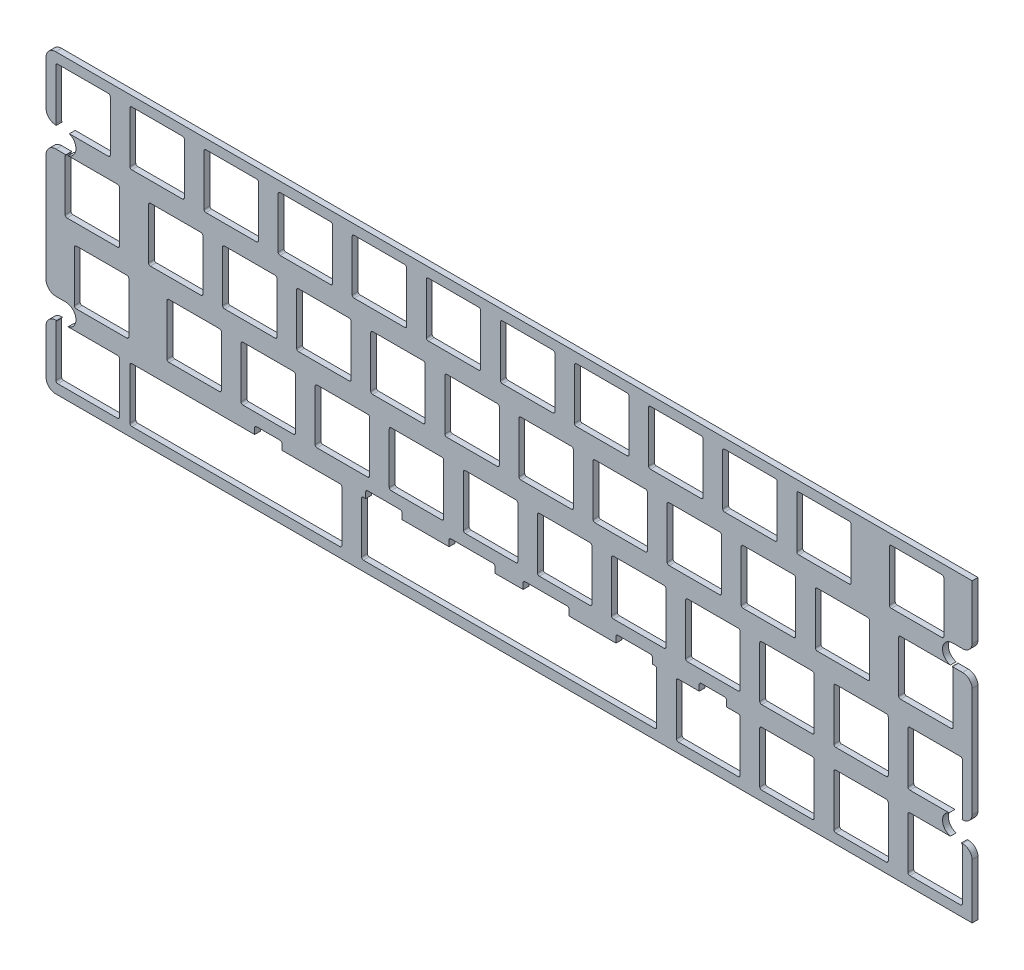
SolidWorks part; units mm, degrees
material "Brass"
ref_plane "Front Plane" through (0, 0, 0) normal (0, 0, 1) x (1, 0, 0)
ref_plane "Top Plane" through (0, 0, 0) normal (0, 1, 0) x (1, 0, 0)
ref_plane "Right Plane" through (0, 0, 0) normal (1, 0, 0) x (0, 0, -1)
sketch "Model" plane through (0, 0, 0) normal (0, 0, 1) x (1, 0, 0)
  line L0 (3.025, -2.525) -> (16.025, -2.525)
  line L1 (3.025, -16.525) -> (16.025, -16.525)
  line L2 (2.525, -3.025) -> (2.525, -16.025)
  line L3 (16.525, -3.025) -> (16.525, -16.025)
  line L4 (22.075, -2.525) -> (35.075, -2.525)
  line L5 (22.075, -16.525) -> (35.075, -16.525)
  line L6 (21.575, -3.025) -> (21.575, -16.025)
  line L7 (35.575, -3.025) -> (35.575, -16.025)
  line L8 (41.125, -2.525) -> (54.125, -2.525)
  line L9 (41.125, -16.525) -> (54.125, -16.525)
  line L10 (40.625, -3.025) -> (40.625, -16.025)
  line L11 (54.625, -3.025) -> (54.625, -16.025)
  line L12 (60.175, -2.525) -> (73.175, -2.525)
  line L13 (60.175, -16.525) -> (73.175, -16.525)
  line L14 (59.675, -3.025) -> (59.675, -16.025)
  line L15 (73.675, -3.025) -> (73.675, -16.025)
  line L16 (79.225, -2.525) -> (92.225, -2.525)
  line L17 (79.225, -16.525) -> (92.225, -16.525)
  line L18 (78.725, -3.025) -> (78.725, -16.025)
  line L19 (92.725, -3.025) -> (92.725, -16.025)
  line L20 (98.275, -2.525) -> (111.275, -2.525)
  line L21 (98.275, -16.525) -> (111.275, -16.525)
  line L22 (97.775, -3.025) -> (97.775, -16.025)
  line L23 (111.775, -3.025) -> (111.775, -16.025)
  line L24 (117.325, -2.525) -> (130.325, -2.525)
  line L25 (117.325, -16.525) -> (130.325, -16.525)
  line L26 (116.825, -3.025) -> (116.825, -16.025)
  line L27 (130.825, -3.025) -> (130.825, -16.025)
  line L28 (136.375, -2.525) -> (149.375, -2.525)
  line L29 (136.375, -16.525) -> (149.375, -16.525)
  line L30 (135.875, -3.025) -> (135.875, -16.025)
  line L31 (149.875, -3.025) -> (149.875, -16.025)
  line L32 (155.425, -2.525) -> (168.425, -2.525)
  line L33 (155.425, -16.525) -> (168.425, -16.525)
  line L34 (154.925, -3.025) -> (154.925, -16.025)
  line L35 (168.925, -3.025) -> (168.925, -16.025)
  line L36 (174.475, -2.525) -> (187.475, -2.525)
  line L37 (174.475, -16.525) -> (187.475, -16.525)
  line L38 (173.975, -3.025) -> (173.975, -16.025)
  line L39 (187.975, -3.025) -> (187.975, -16.025)
  line L40 (193.525, -2.525) -> (206.525, -2.525)
  line L41 (193.525, -16.525) -> (206.525, -16.525)
  line L42 (193.025, -3.025) -> (193.025, -16.025)
  line L43 (207.025, -3.025) -> (207.025, -16.025)
  line L44 (217.3375, -2.525) -> (230.3375, -2.525)
  line L45 (217.3375, -16.525) -> (230.3375, -16.525)
  line L46 (216.8375, -3.025) -> (216.8375, -16.025)
  line L47 (230.8375, -3.025) -> (230.8375, -16.025)
  line L48 (5.4063, -21.575) -> (18.4062, -21.575)
  line L49 (5.4063, -35.575) -> (18.4062, -35.575)
  line L50 (4.9062, -22.075) -> (4.9062, -35.075)
  line L51 (18.9062, -22.075) -> (18.9062, -35.075)
  line L52 (26.8375, -21.575) -> (39.8375, -21.575)
  line L53 (26.8375, -35.575) -> (39.8375, -35.575)
  line L54 (26.3375, -22.075) -> (26.3375, -35.075)
  line L55 (40.3375, -22.075) -> (40.3375, -35.075)
  line L56 (45.8875, -21.575) -> (58.8875, -21.575)
  line L57 (45.8875, -35.575) -> (58.8875, -35.575)
  line L58 (45.3875, -22.075) -> (45.3875, -35.075)
  line L59 (59.3875, -22.075) -> (59.3875, -35.075)
  line L60 (64.9375, -21.575) -> (77.9375, -21.575)
  line L61 (64.9375, -35.575) -> (77.9375, -35.575)
  line L62 (64.4375, -22.075) -> (64.4375, -35.075)
  line L63 (78.4375, -22.075) -> (78.4375, -35.075)
  line L64 (83.9875, -21.575) -> (96.9875, -21.575)
  line L65 (83.9875, -35.575) -> (96.9875, -35.575)
  line L66 (83.4875, -22.075) -> (83.4875, -35.075)
  line L67 (97.4875, -22.075) -> (97.4875, -35.075)
  line L68 (103.0375, -21.575) -> (116.0375, -21.575)
  line L69 (103.0375, -35.575) -> (116.0375, -35.575)
  line L70 (102.5375, -22.075) -> (102.5375, -35.075)
  line L71 (116.5375, -22.075) -> (116.5375, -35.075)
  line L72 (122.0875, -21.575) -> (135.0875, -21.575)
  line L73 (122.0875, -35.575) -> (135.0875, -35.575)
  line L74 (121.5875, -22.075) -> (121.5875, -35.075)
  line L75 (135.5875, -22.075) -> (135.5875, -35.075)
  line L76 (141.1375, -21.575) -> (154.1375, -21.575)
  line L77 (141.1375, -35.575) -> (154.1375, -35.575)
  line L78 (140.6375, -22.075) -> (140.6375, -35.075)
  line L79 (154.6375, -22.075) -> (154.6375, -35.075)
  line L80 (160.1875, -21.575) -> (173.1875, -21.575)
  line L81 (160.1875, -35.575) -> (173.1875, -35.575)
  line L82 (159.6875, -22.075) -> (159.6875, -35.075)
  line L83 (173.6875, -22.075) -> (173.6875, -35.075)
  line L84 (179.2375, -21.575) -> (192.2375, -21.575)
  line L85 (179.2375, -35.575) -> (192.2375, -35.575)
  line L86 (178.7375, -22.075) -> (178.7375, -35.075)
  line L87 (192.7375, -22.075) -> (192.7375, -35.075)
  line L88 (198.2875, -21.575) -> (211.2875, -21.575)
  line L89 (198.2875, -35.575) -> (211.2875, -35.575)
  line L90 (197.7875, -22.075) -> (197.7875, -35.075)
  line L91 (211.7875, -22.075) -> (211.7875, -35.075)
  line L92 (219.7188, -21.575) -> (232.7188, -21.575)
  line L93 (219.7188, -35.575) -> (232.7188, -35.575)
  line L94 (219.2188, -22.075) -> (219.2188, -35.075)
  line L95 (233.2188, -22.075) -> (233.2188, -35.075)
  line L96 (7.7875, -40.625) -> (20.7875, -40.625)
  line L97 (7.7875, -54.625) -> (20.7875, -54.625)
  line L98 (7.2875, -41.125) -> (7.2875, -54.125)
  line L99 (21.2875, -41.125) -> (21.2875, -54.125)
  line L100 (31.6, -40.625) -> (44.6, -40.625)
  line L101 (31.6, -54.625) -> (44.6, -54.625)
  line L102 (31.1, -41.125) -> (31.1, -54.125)
  line L103 (45.1, -41.125) -> (45.1, -54.125)
  line L104 (50.65, -40.625) -> (63.65, -40.625)
  line L105 (50.65, -54.625) -> (63.65, -54.625)
  line L106 (50.15, -41.125) -> (50.15, -54.125)
  line L107 (64.15, -41.125) -> (64.15, -54.125)
  line L108 (69.7, -40.625) -> (82.7, -40.625)
  line L109 (69.7, -54.625) -> (82.7, -54.625)
  line L110 (69.2, -41.125) -> (69.2, -54.125)
  line L111 (83.2, -41.125) -> (83.2, -54.125)
  line L112 (88.75, -40.625) -> (101.75, -40.625)
  line L113 (88.75, -54.625) -> (101.75, -54.625)
  line L114 (88.25, -41.125) -> (88.25, -54.125)
  line L115 (102.25, -41.125) -> (102.25, -54.125)
  line L116 (107.8, -40.625) -> (120.8, -40.625)
  line L117 (107.8, -54.625) -> (120.8, -54.625)
  line L118 (107.3, -41.125) -> (107.3, -54.125)
  line L119 (121.3, -41.125) -> (121.3, -54.125)
  line L120 (126.85, -40.625) -> (139.85, -40.625)
  line L121 (126.85, -54.625) -> (139.85, -54.625)
  line L122 (126.35, -41.125) -> (126.35, -54.125)
  line L123 (140.35, -41.125) -> (140.35, -54.125)
  line L124 (145.9, -40.625) -> (158.9, -40.625)
  line L125 (145.9, -54.625) -> (158.9, -54.625)
  line L126 (145.4, -41.125) -> (145.4, -54.125)
  line L127 (159.4, -41.125) -> (159.4, -54.125)
  line L128 (164.95, -40.625) -> (177.95, -40.625)
  line L129 (164.95, -54.625) -> (177.95, -54.625)
  line L130 (164.45, -41.125) -> (164.45, -54.125)
  line L131 (178.45, -41.125) -> (178.45, -54.125)
  line L132 (184, -40.625) -> (197, -40.625)
  line L133 (184, -54.625) -> (197, -54.625)
  line L134 (183.5, -41.125) -> (183.5, -54.125)
  line L135 (197.5, -41.125) -> (197.5, -54.125)
  line L136 (203.05, -40.625) -> (216.05, -40.625)
  line L137 (203.05, -54.625) -> (216.05, -54.625)
  line L138 (202.55, -41.125) -> (202.55, -54.125)
  line L139 (216.55, -41.125) -> (216.55, -54.125)
  line L140 (222.1, -40.625) -> (235.1, -40.625)
  line L141 (222.1, -54.625) -> (235.1, -54.625)
  line L142 (221.6, -41.125) -> (221.6, -54.125)
  line L143 (235.6, -41.125) -> (235.6, -54.125)
  line L144 (3.025, -59.675) -> (16.025, -59.675)
  line L145 (3.025, -73.675) -> (16.025, -73.675)
  line L146 (2.525, -60.175) -> (2.525, -73.175)
  line L147 (91.5745, -59.675) -> (94.6063, -59.675)
  line L148 (5.4063, -59.675) -> (18.4062, -59.675)
  line L149 (5.4063, -73.675) -> (18.4062, -73.675)
  line L150 (60.175, -73.675) -> (54.125, -73.675)
  line L151 (18.9062, -60.175) -> (18.9062, -73.175)
  line L152 (22.075, -59.675) -> (35.075, -59.675)
  line L153 (22.075, -73.675) -> (35.075, -73.675)
  line L154 (21.575, -60.175) -> (21.575, -73.175)
  line L156 (29.2188, -59.675) -> (42.2188, -59.675)
  line L157 (29.2188, -73.675) -> (42.2188, -73.675)
  line L158 (115.4505, -59.675) -> (120.8, -59.675)
  line L159 (115.4505, -59.675) -> (122.6745, -59.675)
  line L160 (41.125, -59.675) -> (53.65, -59.675)
  line L161 (41.125, -73.675) -> (54.125, -73.675)
  line L162 (134.5005, -59.675) -> (144.6125, -59.675)
  line L165 (107.8, -73.675) -> (120.8, -73.675)
  line L167 (155.9317, -59.675) -> (156.5188, -59.675)
  line L169 (60.15, -57.675) -> (54.15, -57.675)
  line L170 (60.65, -59.675) -> (60.65, -58.175)
  line L171 (53.65, -59.675) -> (53.65, -58.175)
  line L172 (131.6125, -73.675) -> (125.5625, -73.675)
  line L173 (174.45, -57.675) -> (168.45, -57.675)
  line L174 (174.95, -59.675) -> (174.95, -58.175)
  line L175 (167.95, -59.675) -> (167.95, -58.175)
  line L176 (60.65, -59.675) -> (73.175, -59.675)
  line L177 (60.175, -73.675) -> (73.175, -73.675)
  line L179 (174.95, -59.675) -> (175.5687, -59.675)
  line L180 (62.5562, -59.675) -> (75.5563, -59.675)
  line L181 (62.5562, -73.675) -> (75.5563, -73.675)
  line L182 (174.95, -59.675) -> (177.95, -59.675)
  line L183 (76.0563, -60.175) -> (76.0563, -73.175)
  line L184 (81.6063, -59.675) -> (82.1933, -59.675)
  line L185 (81.6063, -73.675) -> (94.6063, -73.675)
  line L186 (81.1063, -60.175) -> (81.1063, -73.175)
  line L187 (107.8, -73.675) -> (106.5125, -73.675)
  line L188 (91.5745, -59.675) -> (103.6245, -59.675)
  line L189 (91.1312, -73.675) -> (104.1312, -73.675)
  line L193 (88.6933, -57.675) -> (82.6933, -57.675)
  line L195 (82.1933, -59.675) -> (82.1933, -58.175)
  line L197 (112.5692, -57.675) -> (106.5693, -57.675)
  line L200 (93.5125, -59.675) -> (103.6245, -59.675)
  line L201 (93.5125, -73.675) -> (106.5125, -73.675)
  line L205 (91.0745, -57.675) -> (85.0745, -57.675)
  line L206 (91.5745, -59.675) -> (91.5745, -58.175)
  line L209 (114.9505, -57.675) -> (108.9505, -57.675)
  line L210 (115.4505, -59.675) -> (115.4505, -58.175)
  line L213 (112.5625, -73.675) -> (125.5625, -73.675)
  line L217 (110.1245, -57.675) -> (104.1245, -57.675)
  line L219 (103.6245, -59.675) -> (103.6245, -58.175)
  line L221 (134.0005, -57.675) -> (128.0005, -57.675)
  line L222 (134.5005, -59.675) -> (134.5005, -58.175)
  line L224 (134.5005, -59.675) -> (146.5505, -59.675)
  line L225 (133.9938, -73.675) -> (146.9938, -73.675)
  line L229 (131.5557, -57.675) -> (125.5557, -57.675)
  line L233 (155.4317, -57.675) -> (149.4317, -57.675)
  line L234 (155.9317, -59.675) -> (155.9317, -58.175)
  line L237 (131.6125, -73.675) -> (144.6125, -73.675)
  line L241 (129.1745, -57.675) -> (123.1745, -57.675)
  line L243 (122.6745, -59.675) -> (122.6745, -58.175)
  line L245 (153.0505, -57.675) -> (147.0505, -57.675)
  line L247 (146.5505, -59.675) -> (146.5505, -58.175)
  line L248 (143.5188, -59.675) -> (146.5505, -59.675)
  line L249 (143.5188, -73.675) -> (156.5188, -73.675)
  line L251 (157.0188, -60.175) -> (157.0188, -73.175)
  line L252 (162.5687, -59.675) -> (167.95, -59.675)
  line L253 (162.5687, -73.675) -> (175.5687, -73.675)
  line L254 (162.0688, -60.175) -> (162.0688, -73.175)
  line L256 (164.95, -59.675) -> (167.95, -59.675)
  line L257 (164.95, -73.675) -> (177.95, -73.675)
  line L259 (178.45, -60.175) -> (178.45, -73.175)
  line L260 (184, -59.675) -> (197, -59.675)
  line L261 (184, -73.675) -> (197, -73.675)
  line L262 (183.5, -60.175) -> (183.5, -73.175)
  line L263 (197.5, -60.175) -> (197.5, -73.175)
  line L264 (203.05, -59.675) -> (216.05, -59.675)
  line L265 (203.05, -73.675) -> (216.05, -73.675)
  line L266 (202.55, -60.175) -> (202.55, -73.175)
  line L267 (216.55, -60.175) -> (216.55, -73.175)
  line L268 (222.1, -59.675) -> (235.1, -59.675)
  line L269 (222.1, -73.675) -> (235.1, -73.675)
  line L270 (221.6, -60.175) -> (221.6, -73.175)
  line L271 (235.6, -60.175) -> (235.6, -73.175)
  line L272 (2.5, 0) -> (238.125, 0)
  line L273 (2.5, -76.2) -> (238.125, -76.2)
  line L274 (0, -2.5) -> (0, -73.7)
  line L275 (238.125, 0) -> (238.125, -76.2)
  arc A0 (3.025, -2.525) -> (2.525, -3.025) centre (3.025, -3.025) ccw
  arc A1 (16.525, -3.025) -> (16.025, -2.525) centre (16.025, -3.025) ccw
  arc A2 (2.525, -16.025) -> (3.025, -16.525) centre (3.025, -16.025) ccw
  arc A3 (16.025, -16.525) -> (16.525, -16.025) centre (16.025, -16.025) ccw
  arc A4 (22.075, -2.525) -> (21.575, -3.025) centre (22.075, -3.025) ccw
  arc A5 (35.575, -3.025) -> (35.075, -2.525) centre (35.075, -3.025) ccw
  arc A6 (21.575, -16.025) -> (22.075, -16.525) centre (22.075, -16.025) ccw
  arc A7 (35.075, -16.525) -> (35.575, -16.025) centre (35.075, -16.025) ccw
  arc A8 (41.125, -2.525) -> (40.625, -3.025) centre (41.125, -3.025) ccw
  arc A9 (54.625, -3.025) -> (54.125, -2.525) centre (54.125, -3.025) ccw
  arc A10 (40.625, -16.025) -> (41.125, -16.525) centre (41.125, -16.025) ccw
  arc A11 (54.125, -16.525) -> (54.625, -16.025) centre (54.125, -16.025) ccw
  arc A12 (60.175, -2.525) -> (59.675, -3.025) centre (60.175, -3.025) ccw
  arc A13 (73.675, -3.025) -> (73.175, -2.525) centre (73.175, -3.025) ccw
  arc A14 (59.675, -16.025) -> (60.175, -16.525) centre (60.175, -16.025) ccw
  arc A15 (73.175, -16.525) -> (73.675, -16.025) centre (73.175, -16.025) ccw
  arc A16 (79.225, -2.525) -> (78.725, -3.025) centre (79.225, -3.025) ccw
  arc A17 (92.725, -3.025) -> (92.225, -2.525) centre (92.225, -3.025) ccw
  arc A18 (78.725, -16.025) -> (79.225, -16.525) centre (79.225, -16.025) ccw
  arc A19 (92.225, -16.525) -> (92.725, -16.025) centre (92.225, -16.025) ccw
  arc A20 (98.275, -2.525) -> (97.775, -3.025) centre (98.275, -3.025) ccw
  arc A21 (111.775, -3.025) -> (111.275, -2.525) centre (111.275, -3.025) ccw
  arc A22 (97.775, -16.025) -> (98.275, -16.525) centre (98.275, -16.025) ccw
  arc A23 (111.275, -16.525) -> (111.775, -16.025) centre (111.275, -16.025) ccw
  arc A24 (117.325, -2.525) -> (116.825, -3.025) centre (117.325, -3.025) ccw
  arc A25 (130.825, -3.025) -> (130.325, -2.525) centre (130.325, -3.025) ccw
  arc A26 (116.825, -16.025) -> (117.325, -16.525) centre (117.325, -16.025) ccw
  arc A27 (130.325, -16.525) -> (130.825, -16.025) centre (130.325, -16.025) ccw
  arc A28 (136.375, -2.525) -> (135.875, -3.025) centre (136.375, -3.025) ccw
  arc A29 (149.875, -3.025) -> (149.375, -2.525) centre (149.375, -3.025) ccw
  arc A30 (135.875, -16.025) -> (136.375, -16.525) centre (136.375, -16.025) ccw
  arc A31 (149.375, -16.525) -> (149.875, -16.025) centre (149.375, -16.025) ccw
  arc A32 (155.425, -2.525) -> (154.925, -3.025) centre (155.425, -3.025) ccw
  arc A33 (168.925, -3.025) -> (168.425, -2.525) centre (168.425, -3.025) ccw
  arc A34 (154.925, -16.025) -> (155.425, -16.525) centre (155.425, -16.025) ccw
  arc A35 (168.425, -16.525) -> (168.925, -16.025) centre (168.425, -16.025) ccw
  arc A36 (174.475, -2.525) -> (173.975, -3.025) centre (174.475, -3.025) ccw
  arc A37 (187.975, -3.025) -> (187.475, -2.525) centre (187.475, -3.025) ccw
  arc A38 (173.975, -16.025) -> (174.475, -16.525) centre (174.475, -16.025) ccw
  arc A39 (187.475, -16.525) -> (187.975, -16.025) centre (187.475, -16.025) ccw
  arc A40 (193.525, -2.525) -> (193.025, -3.025) centre (193.525, -3.025) ccw
  arc A41 (207.025, -3.025) -> (206.525, -2.525) centre (206.525, -3.025) ccw
  arc A42 (193.025, -16.025) -> (193.525, -16.525) centre (193.525, -16.025) ccw
  arc A43 (206.525, -16.525) -> (207.025, -16.025) centre (206.525, -16.025) ccw
  arc A44 (217.3375, -2.525) -> (216.8375, -3.025) centre (217.3375, -3.025) ccw
  arc A45 (230.8375, -3.025) -> (230.3375, -2.525) centre (230.3375, -3.025) ccw
  arc A46 (216.8375, -16.025) -> (217.3375, -16.525) centre (217.3375, -16.025) ccw
  arc A47 (230.3375, -16.525) -> (230.8375, -16.025) centre (230.3375, -16.025) ccw
  arc A48 (5.4063, -21.575) -> (4.9062, -22.075) centre (5.4063, -22.075) ccw
  arc A49 (18.9062, -22.075) -> (18.4062, -21.575) centre (18.4062, -22.075) ccw
  arc A50 (4.9062, -35.075) -> (5.4063, -35.575) centre (5.4063, -35.075) ccw
  arc A51 (18.4062, -35.575) -> (18.9062, -35.075) centre (18.4062, -35.075) ccw
  arc A52 (26.8375, -21.575) -> (26.3375, -22.075) centre (26.8375, -22.075) ccw
  arc A53 (40.3375, -22.075) -> (39.8375, -21.575) centre (39.8375, -22.075) ccw
  arc A54 (26.3375, -35.075) -> (26.8375, -35.575) centre (26.8375, -35.075) ccw
  arc A55 (39.8375, -35.575) -> (40.3375, -35.075) centre (39.8375, -35.075) ccw
  arc A56 (45.8875, -21.575) -> (45.3875, -22.075) centre (45.8875, -22.075) ccw
  arc A57 (59.3875, -22.075) -> (58.8875, -21.575) centre (58.8875, -22.075) ccw
  arc A58 (45.3875, -35.075) -> (45.8875, -35.575) centre (45.8875, -35.075) ccw
  arc A59 (58.8875, -35.575) -> (59.3875, -35.075) centre (58.8875, -35.075) ccw
  arc A60 (64.9375, -21.575) -> (64.4375, -22.075) centre (64.9375, -22.075) ccw
  arc A61 (78.4375, -22.075) -> (77.9375, -21.575) centre (77.9375, -22.075) ccw
  arc A62 (64.4375, -35.075) -> (64.9375, -35.575) centre (64.9375, -35.075) ccw
  arc A63 (77.9375, -35.575) -> (78.4375, -35.075) centre (77.9375, -35.075) ccw
  arc A64 (83.9875, -21.575) -> (83.4875, -22.075) centre (83.9875, -22.075) ccw
  arc A65 (97.4875, -22.075) -> (96.9875, -21.575) centre (96.9875, -22.075) ccw
  arc A66 (83.4875, -35.075) -> (83.9875, -35.575) centre (83.9875, -35.075) ccw
  arc A67 (96.9875, -35.575) -> (97.4875, -35.075) centre (96.9875, -35.075) ccw
  arc A68 (103.0375, -21.575) -> (102.5375, -22.075) centre (103.0375, -22.075) ccw
  arc A69 (116.5375, -22.075) -> (116.0375, -21.575) centre (116.0375, -22.075) ccw
  arc A70 (102.5375, -35.075) -> (103.0375, -35.575) centre (103.0375, -35.075) ccw
  arc A71 (116.0375, -35.575) -> (116.5375, -35.075) centre (116.0375, -35.075) ccw
  arc A72 (122.0875, -21.575) -> (121.5875, -22.075) centre (122.0875, -22.075) ccw
  arc A73 (135.5875, -22.075) -> (135.0875, -21.575) centre (135.0875, -22.075) ccw
  arc A74 (121.5875, -35.075) -> (122.0875, -35.575) centre (122.0875, -35.075) ccw
  arc A75 (135.0875, -35.575) -> (135.5875, -35.075) centre (135.0875, -35.075) ccw
  arc A76 (141.1375, -21.575) -> (140.6375, -22.075) centre (141.1375, -22.075) ccw
  arc A77 (154.6375, -22.075) -> (154.1375, -21.575) centre (154.1375, -22.075) ccw
  arc A78 (140.6375, -35.075) -> (141.1375, -35.575) centre (141.1375, -35.075) ccw
  arc A79 (154.1375, -35.575) -> (154.6375, -35.075) centre (154.1375, -35.075) ccw
  arc A80 (160.1875, -21.575) -> (159.6875, -22.075) centre (160.1875, -22.075) ccw
  arc A81 (173.6875, -22.075) -> (173.1875, -21.575) centre (173.1875, -22.075) ccw
  arc A82 (159.6875, -35.075) -> (160.1875, -35.575) centre (160.1875, -35.075) ccw
  arc A83 (173.1875, -35.575) -> (173.6875, -35.075) centre (173.1875, -35.075) ccw
  arc A84 (179.2375, -21.575) -> (178.7375, -22.075) centre (179.2375, -22.075) ccw
  arc A85 (192.7375, -22.075) -> (192.2375, -21.575) centre (192.2375, -22.075) ccw
  arc A86 (178.7375, -35.075) -> (179.2375, -35.575) centre (179.2375, -35.075) ccw
  arc A87 (192.2375, -35.575) -> (192.7375, -35.075) centre (192.2375, -35.075) ccw
  arc A88 (198.2875, -21.575) -> (197.7875, -22.075) centre (198.2875, -22.075) ccw
  arc A89 (211.7875, -22.075) -> (211.2875, -21.575) centre (211.2875, -22.075) ccw
  arc A90 (197.7875, -35.075) -> (198.2875, -35.575) centre (198.2875, -35.075) ccw
  arc A91 (211.2875, -35.575) -> (211.7875, -35.075) centre (211.2875, -35.075) ccw
  arc A92 (219.7188, -21.575) -> (219.2188, -22.075) centre (219.7188, -22.075) ccw
  arc A93 (233.2188, -22.075) -> (232.7188, -21.575) centre (232.7188, -22.075) ccw
  arc A94 (219.2188, -35.075) -> (219.7188, -35.575) centre (219.7188, -35.075) ccw
  arc A95 (232.7188, -35.575) -> (233.2188, -35.075) centre (232.7188, -35.075) ccw
  arc A96 (7.7875, -40.625) -> (7.2875, -41.125) centre (7.7875, -41.125) ccw
  arc A97 (21.2875, -41.125) -> (20.7875, -40.625) centre (20.7875, -41.125) ccw
  arc A98 (7.2875, -54.125) -> (7.7875, -54.625) centre (7.7875, -54.125) ccw
  arc A99 (20.7875, -54.625) -> (21.2875, -54.125) centre (20.7875, -54.125) ccw
  arc A100 (31.6, -40.625) -> (31.1, -41.125) centre (31.6, -41.125) ccw
  arc A101 (45.1, -41.125) -> (44.6, -40.625) centre (44.6, -41.125) ccw
  arc A102 (31.1, -54.125) -> (31.6, -54.625) centre (31.6, -54.125) ccw
  arc A103 (44.6, -54.625) -> (45.1, -54.125) centre (44.6, -54.125) ccw
  arc A104 (50.65, -40.625) -> (50.15, -41.125) centre (50.65, -41.125) ccw
  arc A105 (64.15, -41.125) -> (63.65, -40.625) centre (63.65, -41.125) ccw
  arc A106 (50.15, -54.125) -> (50.65, -54.625) centre (50.65, -54.125) ccw
  arc A107 (63.65, -54.625) -> (64.15, -54.125) centre (63.65, -54.125) ccw
  arc A108 (69.7, -40.625) -> (69.2, -41.125) centre (69.7, -41.125) ccw
  arc A109 (83.2, -41.125) -> (82.7, -40.625) centre (82.7, -41.125) ccw
  arc A110 (69.2, -54.125) -> (69.7, -54.625) centre (69.7, -54.125) ccw
  arc A111 (82.7, -54.625) -> (83.2, -54.125) centre (82.7, -54.125) ccw
  arc A112 (88.75, -40.625) -> (88.25, -41.125) centre (88.75, -41.125) ccw
  arc A113 (102.25, -41.125) -> (101.75, -40.625) centre (101.75, -41.125) ccw
  arc A114 (88.25, -54.125) -> (88.75, -54.625) centre (88.75, -54.125) ccw
  arc A115 (101.75, -54.625) -> (102.25, -54.125) centre (101.75, -54.125) ccw
  arc A116 (107.8, -40.625) -> (107.3, -41.125) centre (107.8, -41.125) ccw
  arc A117 (121.3, -41.125) -> (120.8, -40.625) centre (120.8, -41.125) ccw
  arc A118 (107.3, -54.125) -> (107.8, -54.625) centre (107.8, -54.125) ccw
  arc A119 (120.8, -54.625) -> (121.3, -54.125) centre (120.8, -54.125) ccw
  arc A120 (126.85, -40.625) -> (126.35, -41.125) centre (126.85, -41.125) ccw
  arc A121 (140.35, -41.125) -> (139.85, -40.625) centre (139.85, -41.125) ccw
  arc A122 (126.35, -54.125) -> (126.85, -54.625) centre (126.85, -54.125) ccw
  arc A123 (139.85, -54.625) -> (140.35, -54.125) centre (139.85, -54.125) ccw
  arc A124 (145.9, -40.625) -> (145.4, -41.125) centre (145.9, -41.125) ccw
  arc A125 (159.4, -41.125) -> (158.9, -40.625) centre (158.9, -41.125) ccw
  arc A126 (145.4, -54.125) -> (145.9, -54.625) centre (145.9, -54.125) ccw
  arc A127 (158.9, -54.625) -> (159.4, -54.125) centre (158.9, -54.125) ccw
  arc A128 (164.95, -40.625) -> (164.45, -41.125) centre (164.95, -41.125) ccw
  arc A129 (178.45, -41.125) -> (177.95, -40.625) centre (177.95, -41.125) ccw
  arc A130 (164.45, -54.125) -> (164.95, -54.625) centre (164.95, -54.125) ccw
  arc A131 (177.95, -54.625) -> (178.45, -54.125) centre (177.95, -54.125) ccw
  arc A132 (184, -40.625) -> (183.5, -41.125) centre (184, -41.125) ccw
  arc A133 (197.5, -41.125) -> (197, -40.625) centre (197, -41.125) ccw
  arc A134 (183.5, -54.125) -> (184, -54.625) centre (184, -54.125) ccw
  arc A135 (197, -54.625) -> (197.5, -54.125) centre (197, -54.125) ccw
  arc A136 (203.05, -40.625) -> (202.55, -41.125) centre (203.05, -41.125) ccw
  arc A137 (216.55, -41.125) -> (216.05, -40.625) centre (216.05, -41.125) ccw
  arc A138 (202.55, -54.125) -> (203.05, -54.625) centre (203.05, -54.125) ccw
  arc A139 (216.05, -54.625) -> (216.55, -54.125) centre (216.05, -54.125) ccw
  arc A140 (222.1, -40.625) -> (221.6, -41.125) centre (222.1, -41.125) ccw
  arc A141 (235.6, -41.125) -> (235.1, -40.625) centre (235.1, -41.125) ccw
  arc A142 (221.6, -54.125) -> (222.1, -54.625) centre (222.1, -54.125) ccw
  arc A143 (235.1, -54.625) -> (235.6, -54.125) centre (235.1, -54.125) ccw
  arc A144 (3.025, -59.675) -> (2.525, -60.175) centre (3.025, -60.175) ccw
  arc A145 (0, -2.5) -> (2.5, 0) centre (2.5, -2.5) cw
  arc A146 (2.525, -73.175) -> (3.025, -73.675) centre (3.025, -73.175) ccw
  arc A147 (2.5, -76.2) -> (0, -73.7) centre (2.5, -73.7) cw
  arc A149 (18.9062, -60.175) -> (18.4062, -59.675) centre (18.4062, -60.175) ccw
  arc A151 (18.4062, -73.675) -> (18.9062, -73.175) centre (18.4062, -73.175) ccw
  arc A152 (22.075, -59.675) -> (21.575, -60.175) centre (22.075, -60.175) ccw
  arc A154 (21.575, -73.175) -> (22.075, -73.675) centre (22.075, -73.175) ccw
  arc A170 (60.65, -58.175) -> (60.15, -57.675) centre (60.15, -58.175) ccw
  arc A171 (54.15, -57.675) -> (53.65, -58.175) centre (54.15, -58.175) ccw
  arc A174 (174.95, -58.175) -> (174.45, -57.675) centre (174.45, -58.175) ccw
  arc A175 (168.45, -57.675) -> (167.95, -58.175) centre (168.45, -58.175) ccw
  arc A181 (76.0563, -60.175) -> (75.5563, -59.675) centre (75.5563, -60.175) ccw
  arc A183 (75.5563, -73.675) -> (76.0563, -73.175) centre (75.5563, -73.175) ccw
  arc A184 (81.6063, -59.675) -> (81.1063, -60.175) centre (81.6063, -60.175) ccw
  arc A186 (81.1063, -73.175) -> (81.6063, -73.675) centre (81.6063, -73.175) ccw
  arc A195 (82.6933, -57.675) -> (82.1933, -58.175) centre (82.6933, -58.175) ccw
  arc A206 (91.5745, -58.175) -> (91.0745, -57.675) centre (91.0745, -58.175) ccw
  arc A210 (115.4505, -58.175) -> (114.9505, -57.675) centre (114.9505, -58.175) ccw
  arc A219 (104.1245, -57.675) -> (103.6245, -58.175) centre (104.1245, -58.175) ccw
  arc A222 (134.5005, -58.175) -> (134.0005, -57.675) centre (134.0005, -58.175) ccw
  arc A234 (155.9317, -58.175) -> (155.4317, -57.675) centre (155.4317, -58.175) ccw
  arc A243 (123.1745, -57.675) -> (122.6745, -58.175) centre (123.1745, -58.175) ccw
  arc A247 (147.0505, -57.675) -> (146.5505, -58.175) centre (147.0505, -58.175) ccw
  arc A249 (157.0188, -60.175) -> (156.5188, -59.675) centre (156.5188, -60.175) ccw
  arc A251 (156.5188, -73.675) -> (157.0188, -73.175) centre (156.5188, -73.175) ccw
  arc A252 (162.5687, -59.675) -> (162.0688, -60.175) centre (162.5687, -60.175) ccw
  arc A254 (162.0688, -73.175) -> (162.5687, -73.675) centre (162.5687, -73.175) ccw
  arc A257 (178.45, -60.175) -> (177.95, -59.675) centre (177.95, -60.175) ccw
  arc A259 (177.95, -73.675) -> (178.45, -73.175) centre (177.95, -73.175) ccw
  arc A260 (184, -59.675) -> (183.5, -60.175) centre (184, -60.175) ccw
  arc A261 (197.5, -60.175) -> (197, -59.675) centre (197, -60.175) ccw
  arc A262 (183.5, -73.175) -> (184, -73.675) centre (184, -73.175) ccw
  arc A263 (197, -73.675) -> (197.5, -73.175) centre (197, -73.175) ccw
  arc A264 (203.05, -59.675) -> (202.55, -60.175) centre (203.05, -60.175) ccw
  arc A265 (216.55, -60.175) -> (216.05, -59.675) centre (216.05, -60.175) ccw
  arc A266 (202.55, -73.175) -> (203.05, -73.675) centre (203.05, -73.175) ccw
  arc A267 (216.05, -73.675) -> (216.55, -73.175) centre (216.05, -73.175) ccw
  arc A268 (222.1, -59.675) -> (221.6, -60.175) centre (222.1, -60.175) ccw
  arc A269 (235.6, -60.175) -> (235.1, -59.675) centre (235.1, -60.175) ccw
  arc A270 (221.6, -73.175) -> (222.1, -73.675) centre (222.1, -73.175) ccw
  arc A271 (235.1, -73.675) -> (235.6, -73.175) centre (235.1, -73.175) ccw
  point P475 (3.8, -19)
  point P479 (3.8, -57.1)
  point P480 (234.4, -57.1)
  point P482 (234.4, -19)
  dimension "D1" = 2.5
  dimension "D2" = 19
  dimension "D3" = 3.8
  dimension "D4" = 3.8
  dimension "D5" = 57.1
  dimension "D6" = 19
  dimension "D7" = 57.1
  dimension "D8" = 234.4
  dimension "D9" = 234.4
extrude "Boss-Extrude1" add sketch "Model" along normal blind 1.5 contours A147 L273 L275 L272 A145 L274 A271 L269 A270 L270 A268 L268 A269 L271 A267 L265 A266 L266 A264 L264 A265 L267 A263 L261 A262 L262 A260 L260 A261 L263 A259 L257 L253 A254 L254 A252 L252 L175 A175 L173 A174 L174 L179 L182 A257 region at (120.7837, -35.979, 0)
sketch "Sketch2" plane through (0, 0, 1.5) normal (0, 0, 1) x (1, 0, 0)
  line L0 (0, -2.5) -> (0, -73.7) construction
  line L1 (2.5, 0) -> (238.125, 0) construction
  line L2 (2.55, -19) -> (5.05, -19) construction
  line L3 (2.55, -17.75) -> (5.05, -17.75) construction
  line L4 (2.55, -20.25) -> (5.05, -20.25) construction
  line L5 (2.55, -57.1) -> (5.05, -57.1) construction
  line L6 (2.55, -55.85) -> (5.05, -55.85) construction
  line L7 (2.55, -58.35) -> (5.05, -58.35) construction
  line L8 (235.65, -57.1) -> (233.15, -57.1) construction
  line L9 (235.65, -58.35) -> (233.15, -58.35) construction
  line L10 (235.65, -55.85) -> (233.15, -55.85) construction
  line L11 (2.55, -16.35) -> (5.05, -16.35)
  line L12 (235.65, -19) -> (233.15, -19) construction
  line L13 (235.65, -20.25) -> (233.15, -20.25) construction
  line L14 (235.65, -17.75) -> (233.15, -17.75) construction
  line L15 (2.55, -21.65) -> (5.05, -21.65)
  line L16 (2.55, -54.45) -> (5.05, -54.45)
  line L17 (2.55, -59.75) -> (5.05, -59.75)
  line L18 (235.65, -59.75) -> (233.15, -59.75)
  line L19 (235.65, -54.45) -> (233.15, -54.45)
  line L20 (235.65, -21.65) -> (233.15, -21.65)
  line L21 (235.65, -16.35) -> (233.15, -16.35)
  line L22 (235.65, -16.35) -> (238.125, -16.35) construction
  line L23 (238.125, 0) -> (238.125, -76.2) construction
  line L24 (235.65, -21.65) -> (238.125, -21.65) construction
  line L25 (235.65, -16.35) -> (235.65, -13.87) construction
  line L26 (235.65, -21.65) -> (235.65, -24.13) construction
  line L27 (238.125, -23.9726) -> (238.125, -16.35)
  line L28 (238.125, -14.0274) -> (238.125, -23.9726)
  line L29 (235.65, -54.45) -> (235.65, -51.97) construction
  line L30 (235.65, -59.75) -> (235.65, -62.23)
  line L31 (238.125, -62.0726) -> (238.125, -52.1274)
  line L32 (2.55, -54.45) -> (0, -54.45) construction
  line L33 (2.55, -54.45) -> (2.55, -51.9) construction
  line L34 (2.55, -59.75) -> (2.55, -62.3)
  line L35 (0, -62.3) -> (0, -51.9)
  line L36 (2.55, -16.35) -> (2.55, -13.8) construction
  line L37 (2.55, -21.65) -> (2.55, -24.2) construction
  line L38 (0, -24.2) -> (0, -13.8)
  arc A0 (2.55, -17.75) -> (2.55, -20.25) centre (2.55, -19) ccw construction
  arc A1 (5.05, -20.25) -> (5.05, -17.75) centre (5.05, -19) ccw construction
  arc A2 (2.55, -55.85) -> (2.55, -58.35) centre (2.55, -57.1) ccw construction
  arc A3 (5.05, -58.35) -> (5.05, -55.85) centre (5.05, -57.1) ccw construction
  arc A4 (235.65, -58.35) -> (235.65, -55.85) centre (235.65, -57.1) ccw construction
  arc A5 (233.15, -55.85) -> (233.15, -58.35) centre (233.15, -57.1) ccw construction
  arc A6 (235.65, -20.25) -> (235.65, -17.75) centre (235.65, -19) ccw construction
  arc A7 (233.15, -17.75) -> (233.15, -20.25) centre (233.15, -19) ccw construction
  arc A8 (5.05, -21.65) -> (5.05, -16.35) centre (5.05, -19) ccw
  arc A10 (5.05, -59.75) -> (5.05, -54.45) centre (5.05, -57.1) ccw
  arc A12 (233.15, -54.45) -> (233.15, -59.75) centre (233.15, -57.1) ccw
  arc A14 (233.15, -16.35) -> (233.15, -21.65) centre (233.15, -19) ccw
  arc A16 (235.65, -16.35) -> (238.125, -14.0274) centre (235.65, -13.87) ccw
  arc A17 (235.65, -21.65) -> (238.125, -23.9726) centre (235.65, -24.13) cw
  arc A18 (235.65, -21.65) -> (235.65, -16.35) centre (235.65, -19) ccw construction
  arc A19 (235.65, -54.45) -> (238.125, -52.1274) centre (235.65, -51.97) ccw
  arc A20 (235.65, -59.75) -> (238.125, -62.0726) centre (235.65, -62.23) cw
  arc A21 (235.65, -59.75) -> (235.65, -54.45) centre (235.65, -57.1) ccw construction
  arc A22 (2.55, -54.45) -> (0, -51.9) centre (2.55, -51.9) cw
  arc A23 (2.55, -59.75) -> (0, -62.3) centre (2.55, -62.3) ccw
  arc A24 (2.55, -54.45) -> (2.55, -59.75) centre (2.55, -57.1) ccw construction
  arc A25 (2.55, -16.35) -> (0, -13.8) centre (2.55, -13.8) cw
  arc A26 (2.55, -21.65) -> (0, -24.2) centre (2.55, -24.2) ccw
  arc A27 (2.55, -16.35) -> (2.55, -21.65) centre (2.55, -19) ccw construction
  point P0 (3.8, -19)
  point P1 (3.8, -57.1)
  point P6 (234.4, -19)
  point P7 (234.4, -57.1)
  point P10 (3.8, -19)
  point P17 (3.8, -57.1)
  point P24 (234.4, -57.1)
  point P31 (234.4, -19)
  dimension "D12" = 2.5
  dimension "D14" = 2.5
  dimension "D16" = 2.5
  dimension "D1" = 3.8
  dimension "D2" = 19
  dimension "D3" = 57.1
  dimension "D4" = 3.8
  dimension "D5" = 234.4
  dimension "D6" = 19
  dimension "D7" = 234.4
  dimension "D8" = 57.1
  dimension "D9" = 2.5
  dimension "D10" = 2.5
  dimension "D11" = 2.5
  dimension "D13" = 2.5
  dimension "D15" = 2.5
  dimension "D18" = 2.48
  dimension "D19" = 2.48
  dimension "D20" = 2.48
  dimension "D21" = 2.48
  dimension "D22" = 2.55
  dimension "D23" = 2.55
  dimension "D24" = 2.55
  dimension "D25" = 2.55
  dimension "D17" = 1.4
extrude "Cut-Extrude1" cut sketch "Sketch2" against normal blind 1.5 contours A26 L15 A8 L11 A25 L38 | A23 L17 A10 L16 A22 L35 | L20 A17 L27 L28 A16 L21 A14 | A20 L31 A19 L19 A12 L18 region at (3.3825, -19, 1.5) region at (3.3825, -57.1, 1.5) region at (234.7681, -19, 1.5)
